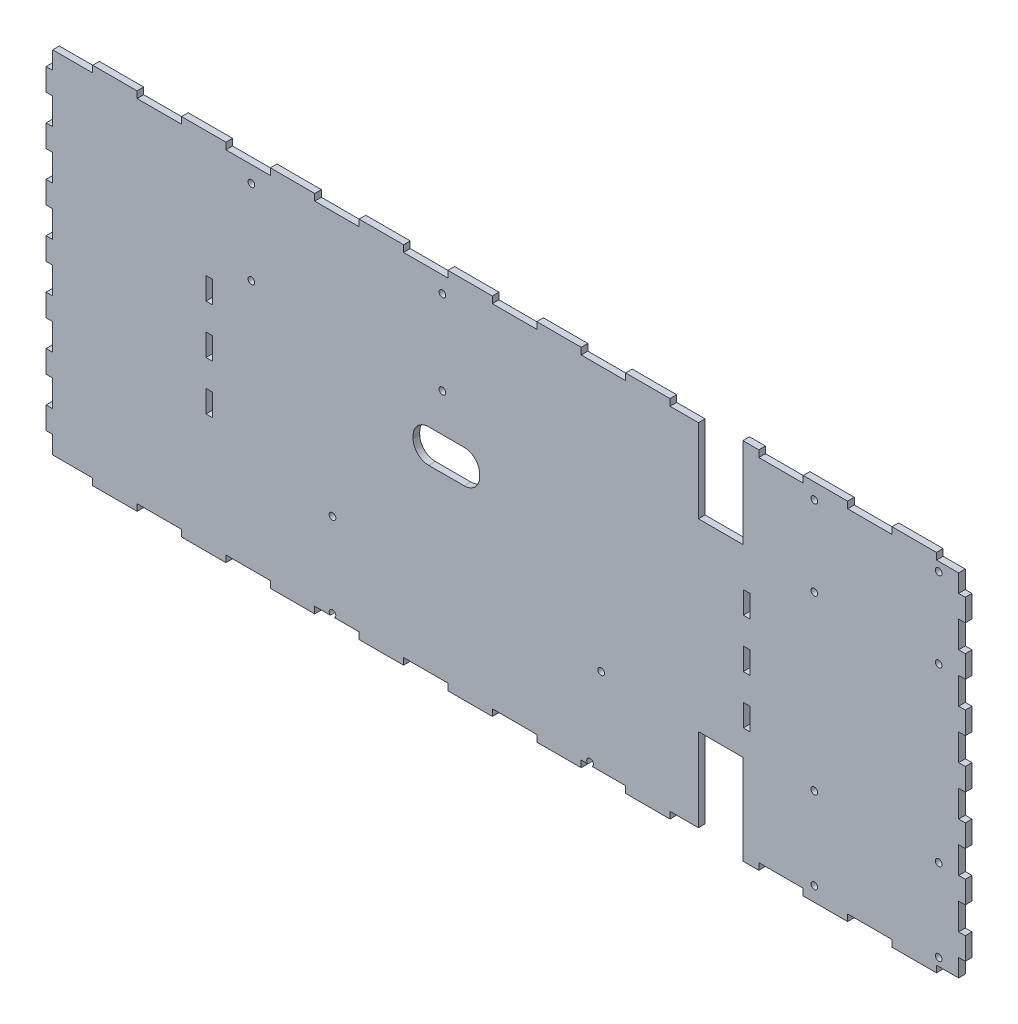
SolidWorks part; units mm, degrees
material "birch 3mm plywood"
ref_plane "Front Plane" through (0, 0, 0) normal (0, 0, 1) x (1, 0, 0)
ref_plane "Top Plane" through (0, 0, 0) normal (0, 1, 0) x (1, 0, 0)
ref_plane "Right Plane" through (0, 0, 0) normal (1, 0, 0) x (0, 0, -1)
sketch "Sketch1" plane through (0, 0, 152) normal (0, 0, 1) x (1, 0, 0)
  line L1 (-207, 82) -> (207, 82)
  line L2 (-207, 82) -> (-207, -82)
  line L3 (-207, -82) -> (207, -82)
  line L4 (207, 82) -> (207, -82)
  line L12 (200, -75) -> (-200, -75) construction
  line L13 (200, 75) -> (200, -75) construction
  line L14 (-200, -75) -> (-200, 75) construction
  line L15 (-200, 75) -> (200, 75) construction
  line L26 (-200, 0) -> (200, 0) construction
  line L31 (-200, 0) -> (200, 0) construction
  point P14 (0, 0)
  point P15 (0, 0)
  point P32 (-47.5, -25.9413)
  point P35 (256.981, -145.9413)
  point P38 (10.8894, 25.9413)
  point P51 (10.8894, -25.9413)
  point P54 (256.981, 145.9413)
  dimension "D1" = 7
  dimension "D2" = 7
  dimension "D3" = 7
  dimension "D4" = 7
  dimension "D5" = 150
  dimension "D6" = 400
extrude "Boss-Extrude1" add sketch "Sketch1" along normal blind 3
sketch "Sketch2" plane through (-207, 0, 0) normal (-1, 0, 0) x (0, 0, 1)
  line L7 (155, -82) -> (152, -82)
  line L8 (152, -82) -> (152, -71)
  line L9 (152, 82) -> (155, 82)
  line L10 (155, 82) -> (155, 71)
  line L11 (152, -61) -> (152, -49)
  line L12 (155, -71) -> (155, -82)
  line L13 (155, -49) -> (155, -61)
  line L14 (152, -39) -> (152, -27)
  line L15 (152, -17) -> (152, -5)
  line L16 (155, -27) -> (155, -39)
  line L17 (155, -5) -> (155, -17)
  line L18 (152, 5) -> (152, 17)
  line L19 (152, 27) -> (152, 39)
  line L20 (155, 17) -> (155, 5)
  line L21 (155, 39) -> (155, 27)
  line L22 (152, 49) -> (152, 61)
  line L23 (152, 71) -> (152, 82)
  line L24 (155, 61) -> (155, 49)
  line L76 (132.5, 88.6) -> (132.5, 93.6)
  line L77 (132.5, 88.6) -> (132.5, 93.6)
  line L78 (129.5, 98.6) -> (128.8771, 98.6)
  line L79 (129.5, 98.6) -> (128.8771, 98.6)
  line L80 (129.5, 82) -> (129.5, 88.6)
  line L81 (129.5, 82) -> (129.5, 88.6)
  line L82 (129.5, 88.6) -> (132.5, 88.6)
  line L83 (129.5, 88.6) -> (132.5, 88.6)
  line L85 (16, 82) -> (16, -82)
  line L102 (129.5, -82) -> (133, -82)
  line L103 (133, -82) -> (133, -79)
  line L104 (133, -79) -> (145, -79)
  line L105 (145, -79) -> (145, -82)
  line L106 (145, -82) -> (155, -82)
  line L107 (155, -82) -> (155, -71)
  line L108 (155, -71) -> (152, -71)
  line L109 (152, -71) -> (152, -61)
  line L110 (152, -61) -> (155, -61)
  line L111 (155, -61) -> (155, -49)
  line L112 (155, -49) -> (152, -49)
  line L113 (152, -49) -> (152, -39)
  line L114 (152, -39) -> (155, -39)
  line L115 (155, -39) -> (155, -27)
  line L116 (155, -27) -> (152, -27)
  line L117 (152, -27) -> (152, -17)
  line L118 (152, -17) -> (155, -17)
  line L119 (155, -17) -> (155, -5)
  line L120 (155, -5) -> (152, -5)
  line L121 (152, -5) -> (152, 5)
  line L122 (152, 5) -> (155, 5)
  line L123 (155, 5) -> (155, 17)
  line L124 (155, 17) -> (152, 17)
  line L125 (152, 17) -> (152, 27)
  line L126 (152, 27) -> (155, 27)
  line L127 (155, 27) -> (155, 39)
  line L128 (155, 39) -> (152, 39)
  line L129 (152, 39) -> (152, 49)
  line L130 (152, 49) -> (155, 49)
  line L131 (155, 49) -> (155, 61)
  line L132 (155, 61) -> (152, 61)
  line L133 (152, 61) -> (152, 71)
  line L134 (152, 71) -> (155, 71)
  line L135 (155, 71) -> (155, 82)
  line L136 (155, 82) -> (145, 82)
  line L137 (145, 82) -> (145, 79)
  line L138 (145, 79) -> (133, 79)
  line L139 (133, 79) -> (133, 82)
  line L140 (133, 82) -> (129.5, 82)
  line L184 (155, -71) -> (152, -71)
  line L186 (152, -61) -> (155, -61)
  line L188 (155, -49) -> (152, -49)
  line L190 (152, -39) -> (155, -39)
  line L192 (155, -27) -> (152, -27)
  line L194 (152, -17) -> (155, -17)
  line L196 (155, -5) -> (152, -5)
  line L198 (152, 5) -> (155, 5)
  line L200 (155, 17) -> (152, 17)
  line L202 (152, 27) -> (155, 27)
  line L204 (155, 39) -> (152, 39)
  line L206 (152, 49) -> (155, 49)
  line L208 (155, 61) -> (152, 61)
  line L210 (152, 71) -> (155, 71)
  line L297 (132.5, 93.6) -> (129.5, 93.6)
  line L298 (132.5, 93.6) -> (129.5, 93.6)
  line L299 (129.5, 93.6) -> (129.5, 98.6)
  line L300 (129.5, 93.6) -> (129.5, 98.6)
  line L301 (128.8771, -98.6) -> (129.5, -98.6)
  line L302 (128.8771, -98.6) -> (129.5, -98.6)
  line L303 (129.5, -98.6) -> (129.5, -93.6)
  line L304 (129.5, -98.6) -> (129.5, -93.6)
  line L305 (129.5, -93.6) -> (132.5, -93.6)
  line L306 (129.5, -93.6) -> (132.5, -93.6)
  line L307 (132.5, -93.6) -> (132.5, -88.6)
  line L308 (132.5, -93.6) -> (132.5, -88.6)
  line L309 (132.5, -88.6) -> (129.5, -88.6)
  line L310 (132.5, -88.6) -> (129.5, -88.6)
  line L311 (129.5, -88.6) -> (129.5, -82)
  line L312 (129.5, -88.6) -> (129.5, -82)
  arc A4 (128.8771, 98.6) -> (16, 82) centre (128.8771, -293.4723) ccw
  arc A5 (128.8771, 98.6) -> (16, 82) centre (128.8771, -293.4723) ccw
  arc A6 (16, -82) -> (128.8771, -98.6) centre (128.8771, 293.4723) ccw
  arc A7 (16, -82) -> (128.8771, -98.6) centre (128.8771, 293.4723) ccw
  line M77 (152, 82) -> (152, -82)
  line M78 (152, -82) -> (155, -82)
  line M79 (155, -82) -> (155, 82)
  line M80 (155, 82) -> (152, 82)
  dimension "D1" = 0
extrude "Cut-Extrude1" cut sketch "Sketch2" against normal blind 3 contours L184 M79 M77 M78 | L188 L186 M79 M77 | L192 L190 M79 M77 | L196 L194 M79 M77 | L200 L198 M79 M77 | L204 L202 M79 M77 | L208 L206 M79 M77 | L210 M77 M79 M80 region at (-207, -76.5, 153.5) region at (-207, -55, 153.5) region at (-207, -33, 153.5) region at (-207, -11, 153.5) region at (-207, 11, 153.5) region at (-207, 33, 153.5) region at (-207, 55, 153.5) region at (-207, 76.5, 153.5)
mirror "Mirror1" about plane through (0, 0, 0) normal (1, 0, 0) of "Cut-Extrude1"
sketch "Sketch3" plane through (0, 82, 0) normal (0, 1, 0) x (1, 0, 0)
  line L92 (174, -152) -> (194, -152)
  line L93 (194, -152) -> (194, -155)
  line L94 (194, -155) -> (204, -155)
  line L97 (207, -45) -> (204, -45)
  line L120 (204, -16) -> (-204, -16)
  line L123 (-204, -45) -> (-207, -45)
  line L146 (-204, -155) -> (-186, -155)
  line L147 (-186, -155) -> (-186, -152)
  line L148 (-186, -152) -> (-166, -152)
  line L149 (-166, -152) -> (-166, -155)
  line L150 (-166, -155) -> (-146, -155)
  line L151 (-146, -155) -> (-146, -152)
  line L152 (-146, -152) -> (-126, -152)
  line L153 (-126, -152) -> (-126, -155)
  line L154 (-126, -155) -> (-106, -155)
  line L155 (-106, -155) -> (-106, -152)
  line L156 (-106, -152) -> (-86, -152)
  line L157 (-86, -152) -> (-86, -155)
  line L158 (-86, -155) -> (-66, -155)
  line L159 (-66, -155) -> (-66, -152)
  line L160 (-66, -152) -> (-46, -152)
  line L161 (-46, -152) -> (-46, -155)
  line L162 (-46, -155) -> (-26, -155)
  line L163 (-26, -155) -> (-26, -152)
  line L164 (-26, -152) -> (-6, -152)
  line L165 (-6, -152) -> (-6, -155)
  line L166 (-6, -155) -> (14, -155)
  line L167 (14, -155) -> (14, -152)
  line L168 (14, -152) -> (34, -152)
  line L169 (34, -152) -> (34, -155)
  line L170 (34, -155) -> (54, -155)
  line L171 (54, -155) -> (54, -152)
  line L172 (54, -152) -> (74, -152)
  line L173 (74, -152) -> (74, -155)
  line L174 (74, -155) -> (94, -155)
  line L175 (94, -155) -> (94, -152)
  line L176 (94, -152) -> (114, -152)
  line L177 (114, -152) -> (114, -155)
  line L178 (114, -155) -> (134, -155)
  line L179 (134, -155) -> (134, -152)
  line L180 (134, -152) -> (154, -152)
  line L181 (154, -152) -> (154, -155)
  line L182 (154, -155) -> (174, -155)
  line L183 (174, -155) -> (174, -152)
  line L184 (174, -152) -> (194, -152)
  line L185 (194, -152) -> (194, -155)
  line L186 (194, -155) -> (204, -155)
  line L212 (204, -16) -> (-204, -16)
  line L238 (-204, -155) -> (-186, -155)
  line L239 (-186, -155) -> (-186, -152)
  line L240 (-186, -152) -> (-166, -152)
  line L241 (-166, -152) -> (-166, -155)
  line L242 (-166, -155) -> (-146, -155)
  line L243 (-146, -155) -> (-146, -152)
  line L244 (-146, -152) -> (-126, -152)
  line L245 (-126, -152) -> (-126, -155)
  line L246 (-126, -155) -> (-106, -155)
  line L247 (-106, -155) -> (-106, -152)
  line L248 (-106, -152) -> (-86, -152)
  line L249 (-86, -152) -> (-86, -155)
  line L250 (-86, -155) -> (-66, -155)
  line L251 (-66, -155) -> (-66, -152)
  line L252 (-66, -152) -> (-46, -152)
  line L253 (-46, -152) -> (-46, -155)
  line L254 (-46, -155) -> (-26, -155)
  line L255 (-26, -155) -> (-26, -152)
  line L256 (-26, -152) -> (-6, -152)
  line L257 (-6, -152) -> (-6, -155)
  line L258 (-6, -155) -> (14, -155)
  line L259 (14, -155) -> (14, -152)
  line L260 (14, -152) -> (34, -152)
  line L261 (34, -152) -> (34, -155)
  line L262 (34, -155) -> (54, -155)
  line L263 (54, -155) -> (54, -152)
  line L264 (54, -152) -> (74, -152)
  line L265 (74, -152) -> (74, -155)
  line L266 (74, -155) -> (94, -155)
  line L267 (94, -155) -> (94, -152)
  line L268 (94, -152) -> (114, -152)
  line L269 (114, -152) -> (114, -155)
  line L270 (114, -155) -> (134, -155)
  line L271 (134, -155) -> (134, -152)
  line L272 (134, -152) -> (154, -152)
  line L273 (154, -152) -> (154, -155)
  line L274 (154, -155) -> (174, -155)
  line L275 (174, -155) -> (174, -152)
  line L576 (-204, -45) -> (-207, -45)
  line L577 (-207, -45) -> (-207, -57)
  line L578 (-207, -45) -> (-207, -57)
  line L579 (-207, -57) -> (-204, -57)
  line L580 (-207, -57) -> (-204, -57)
  line L581 (-204, -57) -> (-204, -67)
  line L582 (-204, -57) -> (-204, -67)
  line L583 (-204, -67) -> (-207, -67)
  line L584 (-204, -67) -> (-207, -67)
  line L585 (-207, -67) -> (-207, -79)
  line L586 (-207, -67) -> (-207, -79)
  line L587 (-207, -79) -> (-204, -79)
  line L588 (-207, -79) -> (-204, -79)
  line L589 (-204, -79) -> (-204, -89)
  line L590 (-204, -79) -> (-204, -89)
  line L591 (-204, -89) -> (-207, -89)
  line L592 (-204, -89) -> (-207, -89)
  line L593 (-207, -89) -> (-207, -101)
  line L594 (-207, -89) -> (-207, -101)
  line L595 (-207, -101) -> (-204, -101)
  line L596 (-207, -101) -> (-204, -101)
  line L597 (-204, -101) -> (-204, -111)
  line L598 (-204, -101) -> (-204, -111)
  line L599 (-204, -111) -> (-207, -111)
  line L600 (-204, -111) -> (-207, -111)
  line L601 (-207, -111) -> (-207, -123)
  line L602 (-207, -111) -> (-207, -123)
  line L603 (-207, -123) -> (-204, -123)
  line L604 (-207, -123) -> (-204, -123)
  line L605 (-204, -123) -> (-204, -133)
  line L606 (-204, -123) -> (-204, -133)
  line L607 (-204, -133) -> (-207, -133)
  line L608 (-204, -133) -> (-207, -133)
  line L609 (-207, -133) -> (-207, -145)
  line L610 (-207, -133) -> (-207, -145)
  line L611 (-207, -145) -> (-204, -145)
  line L612 (-207, -145) -> (-204, -145)
  line L613 (-204, -145) -> (-204, -155)
  line L614 (-204, -145) -> (-204, -155)
  line L615 (-204, -16) -> (-204, -23)
  line L616 (-204, -16) -> (-204, -23)
  line L617 (-204, -23) -> (-207, -23)
  line L618 (-204, -23) -> (-207, -23)
  line L619 (-207, -23) -> (-207, -35)
  line L620 (-207, -23) -> (-207, -35)
  line L621 (-207, -35) -> (-204, -35)
  line L622 (-207, -35) -> (-204, -35)
  line L623 (-204, -35) -> (-204, -45)
  line L624 (-204, -35) -> (-204, -45)
  line L741 (207, -45) -> (204, -45)
  line L742 (204, -45) -> (204, -35)
  line L743 (204, -45) -> (204, -35)
  line L744 (204, -35) -> (207, -35)
  line L745 (204, -35) -> (207, -35)
  line L746 (207, -35) -> (207, -23)
  line L747 (207, -35) -> (207, -23)
  line L748 (207, -23) -> (204, -23)
  line L749 (207, -23) -> (204, -23)
  line L750 (204, -23) -> (204, -16)
  line L751 (204, -23) -> (204, -16)
  line L752 (204, -155) -> (204, -145)
  line L753 (204, -155) -> (204, -145)
  line L754 (204, -145) -> (207, -145)
  line L755 (204, -145) -> (207, -145)
  line L756 (207, -145) -> (207, -133)
  line L757 (207, -145) -> (207, -133)
  line L758 (207, -133) -> (204, -133)
  line L759 (207, -133) -> (204, -133)
  line L760 (204, -133) -> (204, -123)
  line L761 (204, -133) -> (204, -123)
  line L762 (204, -123) -> (207, -123)
  line L763 (204, -123) -> (207, -123)
  line L764 (207, -123) -> (207, -111)
  line L765 (207, -123) -> (207, -111)
  line L766 (207, -111) -> (204, -111)
  line L767 (207, -111) -> (204, -111)
  line L768 (204, -111) -> (204, -101)
  line L769 (204, -111) -> (204, -101)
  line L770 (204, -101) -> (207, -101)
  line L771 (204, -101) -> (207, -101)
  line L772 (207, -101) -> (207, -89)
  line L773 (207, -101) -> (207, -89)
  line L774 (207, -89) -> (204, -89)
  line L775 (207, -89) -> (204, -89)
  line L776 (204, -89) -> (204, -79)
  line L777 (204, -89) -> (204, -79)
  line L778 (204, -79) -> (207, -79)
  line L779 (204, -79) -> (207, -79)
  line L780 (207, -79) -> (207, -67)
  line L781 (207, -79) -> (207, -67)
  line L782 (207, -67) -> (204, -67)
  line L783 (207, -67) -> (204, -67)
  line L784 (204, -67) -> (204, -57)
  line L785 (204, -67) -> (204, -57)
  line L786 (204, -57) -> (207, -57)
  line L787 (204, -57) -> (207, -57)
  line L788 (207, -57) -> (207, -45)
  line L789 (207, -57) -> (207, -45)
  dimension "D1" = 0
extrude "Cut-Extrude2" cut sketch "Sketch3" against normal blind 3
mirror "Mirror2" about plane through (0, 0, 0) normal (0, 1, 0) of "Cut-Extrude2"
sketch "Sketch4" plane through (0, 0, 155) normal (0, 0, 1) x (1, 0, 0)
  line L0 (-132, 25.512) -> (-132, 15.512) construction
  line L1 (-132, 15.512) -> (-135, 15.512) construction
  line L2 (-135, 15.512) -> (-135, 25.512) construction
  line L3 (-135, 25.512) -> (-132, 25.512) construction
  line L4 (-132, 3.512) -> (-132, -6.488) construction
  line L5 (-132, -6.488) -> (-135, -6.488) construction
  line L6 (-135, -6.488) -> (-135, 3.512) construction
  line L7 (-135, 3.512) -> (-132, 3.512) construction
  line L8 (-132, -18.488) -> (-132, -28.488) construction
  line L9 (-132, -28.488) -> (-135, -28.488) construction
  line L10 (-135, -28.488) -> (-135, -18.488) construction
  line L11 (-135, -18.488) -> (-132, -18.488) construction
  line L12 (-132, 25.512) -> (-132, 15.512)
  line L13 (-132, 15.512) -> (-135, 15.512)
  line L14 (-135, 15.512) -> (-135, 25.512)
  line L15 (-135, 25.512) -> (-132, 25.512)
  line L16 (-132, 3.512) -> (-132, -6.488)
  line L17 (-132, -6.488) -> (-135, -6.488)
  line L18 (-135, -6.488) -> (-135, 3.512)
  line L19 (-135, 3.512) -> (-132, 3.512)
  line L20 (-132, -18.488) -> (-132, -28.488)
  line L21 (-132, -28.488) -> (-135, -28.488)
  line L22 (-135, -28.488) -> (-135, -18.488)
  line L23 (-135, -18.488) -> (-132, -18.488)
  line L24 (110, 24.0241) -> (110, 14.0241) construction
  line L25 (110, 14.0241) -> (107, 14.0241) construction
  line L26 (107, 14.0241) -> (107, 24.0241) construction
  line L27 (107, 24.0241) -> (110, 24.0241) construction
  line L28 (110, 2.0241) -> (110, -7.9759) construction
  line L29 (110, -7.9759) -> (107, -7.9759) construction
  line L30 (107, -7.9759) -> (107, 2.0241) construction
  line L31 (107, 2.0241) -> (110, 2.0241) construction
  line L32 (110, -19.9759) -> (110, -29.9759) construction
  line L33 (110, -29.9759) -> (107, -29.9759) construction
  line L34 (107, -29.9759) -> (107, -19.9759) construction
  line L35 (107, -19.9759) -> (110, -19.9759) construction
  line L36 (110, 24.0241) -> (110, 14.0241)
  line L37 (110, 14.0241) -> (107, 14.0241)
  line L38 (107, 14.0241) -> (107, 24.0241)
  line L39 (107, 24.0241) -> (110, 24.0241)
  line L40 (110, 2.0241) -> (110, -7.9759)
  line L41 (110, -7.9759) -> (107, -7.9759)
  line L42 (107, -7.9759) -> (107, 2.0241)
  line L43 (107, 2.0241) -> (110, 2.0241)
  line L44 (110, -19.9759) -> (110, -29.9759)
  line L45 (110, -29.9759) -> (107, -29.9759)
  line L46 (107, -29.9759) -> (107, -19.9759)
  line L47 (107, -19.9759) -> (110, -19.9759)
  circle A0 centre (139, 39) radius 1.5 construction
  circle A1 centre (195, 39) radius 1.5 construction
  circle A2 centre (195, 75) radius 1.5 construction
  circle A3 centre (139, 75) radius 1.5 construction
  circle A4 centre (-114.5, 33.7241) radius 1.5 construction
  circle A5 centre (-114.5, 71.6241) radius 1.5 construction
  circle A6 centre (-28.5, 33.7241) radius 1.5 construction
  circle A7 centre (-28.5, 71.6241) radius 1.5 construction
  circle A8 centre (139, 39) radius 1.5
  circle A9 centre (195, 39) radius 1.5
  circle A10 centre (195, 75) radius 1.5
  circle A11 centre (139, 75) radius 1.5
  circle A16 centre (139, -75.5) radius 1.5
  circle A17 centre (195, -75.5) radius 1.5
  circle A18 centre (195, -38.5) radius 1.5
  circle A19 centre (139, -38.5) radius 1.5
  circle A20 centre (-114.5, 33.7241) radius 1.5
  circle A21 centre (-114.5, 71.6241) radius 1.5
  circle A22 centre (-28.5, 33.7241) radius 1.5
  circle A23 centre (-28.5, 71.6241) radius 1.5
  circle A24 centre (38, -77.8759) radius 1.5 construction
  circle A25 centre (43, -39.9759) radius 1.5 construction
  circle A26 centre (-78, -77.8759) radius 1.5 construction
  circle A27 centre (-78, -39.9759) radius 1.5 construction
  circle A28 centre (38, -77.8759) radius 1.5
  circle A29 centre (43, -39.9759) radius 1.5
  circle A30 centre (-78, -77.8759) radius 1.5
  circle A31 centre (-78, -39.9759) radius 1.5
extrude "Cut-Extrude3" cut sketch "Sketch4" against normal blind 10
sketch "Sketch5" plane through (0, 0, 155) normal (0, 0, 1) x (1, 0, 0)
  line L0 (86.8, 82) -> (86.8, 79) construction
  line L1 (-34.7, 1.6241) -> (-18.7, 1.6241)
  line L2 (-41.7, 8.6241) -> (-41.7, 9.6241)
  line L3 (-34.7, 16.6241) -> (-18.7, 16.6241)
  line L4 (-11.7, 9.6241) -> (-11.7, 8.6241)
  line L5 (-27.7, 1.6241) -> (0, 1.6241) construction
  line L6 (86.8, 41.5) -> (106.8, 41.5)
  line L7 (-27.7, 1.6241) -> (-27.7, -10.7759) construction
  line L8 (86.8, 41.5) -> (86.8, 82)
  line L9 (86.8, 82) -> (106.8, 82)
  line L10 (106.8, 41.5) -> (106.8, 82)
  line L12 (114, 82) -> (94, 82) construction
  line L13 (64, 82) -> (64, -82) construction
  line L14 (74, 82) -> (54, 82) construction
  line L15 (54, -82) -> (74, -82) construction
  line L16 (64, -82) -> (64, 0) construction
  line L17 (64, 0) -> (99.6083, 0) construction
  line L18 (106.8, -41.5) -> (106.8, -82)
  line L19 (86.8, -82) -> (106.8, -82)
  line L20 (86.8, -41.5) -> (106.8, -41.5)
  line L21 (86.8, -41.5) -> (86.8, -82)
  arc A0 (-34.7, 16.6241) -> (-41.7, 9.6241) centre (-34.7, 9.6241) ccw
  arc A1 (-11.7, 9.6241) -> (-18.7, 16.6241) centre (-18.7, 9.6241) ccw
  arc A2 (-18.7, 1.6241) -> (-11.7, 8.6241) centre (-18.7, 8.6241) ccw
  arc A3 (-34.7, 1.6241) -> (-41.7, 8.6241) centre (-34.7, 8.6241) cw
  point P16 (-11.7, 1.6241)
  point P19 (-41.7, 1.6241)
  dimension "D4" = 7
  dimension "D1" = 30
  dimension "D2" = 15
  dimension "D3" = 16
  dimension "D5" = 20
  dimension "D6" = 40.5
extrude "Cut-Extrude4" cut sketch "Sketch5" against normal blind 10
sketch "Sketch6" plane through (0, 0, 155) normal (0, 0, 1) x (1, 0, 0)
  line L0 (-204, 79) -> (-186, 79) construction
  line L1 (-170.906, 59) -> (-176.6795, 69)
  line L2 (-176.6795, 69) -> (-188.2265, 69)
  line L3 (-188.2265, 69) -> (-194, 59)
  line L4 (-194, 59) -> (-188.2265, 49)
  line L5 (-188.2265, 49) -> (-176.6795, 49)
  line L6 (-176.6795, 49) -> (-170.906, 59)
  line L7 (-204, 49) -> (-204, 61) construction
  line L8 (-144.9252, 44) -> (-150.6987, 54)
  line L9 (-150.6987, 54) -> (-162.2457, 54)
  line L10 (-162.2457, 54) -> (-168.0192, 44)
  line L11 (-168.0192, 44) -> (-162.2457, 34)
  line L12 (-162.2457, 34) -> (-150.6987, 34)
  line L13 (-150.6987, 34) -> (-144.9252, 44)
  line L14 (-120.906, 59) -> (-126.6795, 69)
  line L15 (-126.6795, 69) -> (-138.2265, 69)
  line L16 (-138.2265, 69) -> (-144, 59)
  line L17 (-144, 59) -> (-138.2265, 49)
  line L18 (-138.2265, 49) -> (-126.6795, 49)
  line L19 (-126.6795, 49) -> (-120.906, 59)
  line L20 (-94.9252, 44) -> (-100.6987, 54)
  line L21 (-100.6987, 54) -> (-112.2457, 54)
  line L22 (-112.2457, 54) -> (-118.0192, 44)
  line L23 (-118.0192, 44) -> (-112.2457, 34)
  line L24 (-112.2457, 34) -> (-100.6987, 34)
  line L25 (-100.6987, 34) -> (-94.9252, 44)
  line L26 (-70.906, 59) -> (-76.6795, 69)
  line L27 (-76.6795, 69) -> (-88.2265, 69)
  line L28 (-88.2265, 69) -> (-94, 59)
  line L29 (-94, 59) -> (-88.2265, 49)
  line L30 (-88.2265, 49) -> (-76.6795, 49)
  line L31 (-76.6795, 49) -> (-70.906, 59)
  line L32 (-44.9252, 44) -> (-50.6987, 54)
  line L33 (-50.6987, 54) -> (-62.2457, 54)
  line L34 (-62.2457, 54) -> (-68.0192, 44)
  line L35 (-68.0192, 44) -> (-62.2457, 34)
  line L36 (-62.2457, 34) -> (-50.6987, 34)
  line L37 (-50.6987, 34) -> (-44.9252, 44)
  line L38 (-20.906, 59) -> (-26.6795, 69)
  line L39 (-26.6795, 69) -> (-38.2265, 69)
  line L40 (-38.2265, 69) -> (-44, 59)
  line L41 (-44, 59) -> (-38.2265, 49)
  line L42 (-38.2265, 49) -> (-26.6795, 49)
  line L43 (-26.6795, 49) -> (-20.906, 59)
  line L44 (5.0748, 44) -> (-0.6987, 54)
  line L45 (-0.6987, 54) -> (-12.2457, 54)
  line L46 (-12.2457, 54) -> (-18.0192, 44)
  line L47 (-18.0192, 44) -> (-12.2457, 34)
  line L48 (-12.2457, 34) -> (-0.6987, 34)
  line L49 (-0.6987, 34) -> (5.0748, 44)
  line L50 (29.094, 59) -> (23.3205, 69)
  line L51 (23.3205, 69) -> (11.7735, 69)
  line L52 (11.7735, 69) -> (6, 59)
  line L53 (6, 59) -> (11.7735, 49)
  line L54 (11.7735, 49) -> (23.3205, 49)
  line L55 (23.3205, 49) -> (29.094, 59)
  line L56 (55.0748, 44) -> (49.3013, 54)
  line L57 (49.3013, 54) -> (37.7543, 54)
  line L58 (37.7543, 54) -> (31.9808, 44)
  line L59 (31.9808, 44) -> (37.7543, 34)
  line L60 (37.7543, 34) -> (49.3013, 34)
  line L61 (49.3013, 34) -> (55.0748, 44)
  line L62 (79.094, 59) -> (73.3205, 69)
  line L63 (73.3205, 69) -> (61.7735, 69)
  line L64 (61.7735, 69) -> (56, 59)
  line L65 (56, 59) -> (61.7735, 49)
  line L66 (61.7735, 49) -> (73.3205, 49)
  line L67 (73.3205, 49) -> (79.094, 59)
  line L68 (105.0748, 44) -> (99.3013, 54)
  line L69 (99.3013, 54) -> (87.7543, 54)
  line L70 (87.7543, 54) -> (81.9808, 44)
  line L71 (81.9808, 44) -> (87.7543, 34)
  line L72 (87.7543, 34) -> (99.3013, 34)
  line L73 (99.3013, 34) -> (105.0748, 44)
  line L74 (129.094, 59) -> (123.3205, 69)
  line L75 (123.3205, 69) -> (111.7735, 69)
  line L76 (111.7735, 69) -> (106, 59)
  line L77 (106, 59) -> (111.7735, 49)
  line L78 (111.7735, 49) -> (123.3205, 49)
  line L79 (123.3205, 49) -> (129.094, 59)
  line L80 (155.0748, 44) -> (149.3013, 54)
  line L81 (149.3013, 54) -> (137.7543, 54)
  line L82 (137.7543, 54) -> (134.8675, 49)
  line L85 (152.188, 39) -> (155.0748, 44)
  line L86 (179.094, 59) -> (173.3205, 69)
  line L87 (173.3205, 69) -> (161.7735, 69)
  line L88 (161.7735, 69) -> (156, 59)
  line L89 (156, 59) -> (161.7735, 49)
  line L90 (161.7735, 49) -> (173.3205, 49)
  line L91 (173.3205, 49) -> (179.094, 59)
  line L93 (193.5278, 54) -> (187.7543, 54)
  line L94 (187.7543, 54) -> (181.9808, 44)
  line L95 (181.9808, 44) -> (184.8675, 39)
  line L98 (-123.7927, 34) -> (-126.6795, 39)
  line L99 (-126.6795, 39) -> (-138.2265, 39)
  line L100 (-138.2265, 39) -> (-141.1132, 34)
  line L104 (-94.9252, 14) -> (-100.6987, 24)
  line L105 (-100.6987, 24) -> (-112.2457, 24)
  line L106 (-112.2457, 24) -> (-118.0192, 14)
  line L107 (-118.0192, 14) -> (-112.2457, 4)
  line L108 (-112.2457, 4) -> (-100.6987, 4)
  line L109 (-100.6987, 4) -> (-94.9252, 14)
  line L112 (-88.2265, 39) -> (-94, 29)
  line L113 (-94, 29) -> (-88.2265, 19)
  line L114 (-88.2265, 19) -> (-76.6795, 19)
  line L116 (-44.9252, 14) -> (-50.6987, 24)
  line L117 (-50.6987, 24) -> (-62.2457, 24)
  line L118 (-62.2457, 24) -> (-68.0192, 14)
  line L119 (-68.0192, 14) -> (-62.2457, 4)
  line L120 (-62.2457, 4) -> (-50.6987, 4)
  line L121 (-50.6987, 4) -> (-44.9252, 14)
  line L123 (-32.453, 39) -> (-38.2265, 39)
  line L124 (-38.2265, 39) -> (-44, 29)
  line L125 (-44, 29) -> (-41.1132, 24)
  line L128 (5.0748, 14) -> (-0.6987, 24)
  line L129 (-0.6987, 24) -> (-6.4722, 24)
  line L132 (-6.4722, 4) -> (-0.6987, 4)
  line L133 (-0.6987, 4) -> (5.0748, 14)
  line L134 (29.094, 29) -> (23.3205, 39)
  line L135 (23.3205, 39) -> (11.7735, 39)
  line L136 (11.7735, 39) -> (6, 29)
  line L137 (6, 29) -> (11.7735, 19)
  line L138 (11.7735, 19) -> (23.3205, 19)
  line L139 (23.3205, 19) -> (29.094, 29)
  line L140 (55.0748, 14) -> (49.3013, 24)
  line L141 (49.3013, 24) -> (37.7543, 24)
  line L142 (37.7543, 24) -> (31.9808, 14)
  line L143 (31.9808, 14) -> (37.7543, 4)
  line L144 (37.7543, 4) -> (49.3013, 4)
  line L145 (49.3013, 4) -> (55.0748, 14)
  line L146 (79.094, 29) -> (73.3205, 39)
  line L147 (73.3205, 39) -> (61.7735, 39)
  line L148 (61.7735, 39) -> (56, 29)
  line L149 (56, 29) -> (61.7735, 19)
  line L150 (61.7735, 19) -> (73.3205, 19)
  line L151 (73.3205, 19) -> (79.094, 29)
  line L153 (99.3013, 24) -> (87.7543, 24)
  line L154 (87.7543, 24) -> (81.9808, 14)
  line L155 (81.9808, 14) -> (87.7543, 4)
  line L156 (87.7543, 4) -> (99.3013, 4)
  line L158 (129.094, 29) -> (123.3205, 39)
  line L159 (123.3205, 39) -> (117.547, 39)
  line L162 (117.547, 19) -> (123.3205, 19)
  line L163 (123.3205, 19) -> (129.094, 29)
  line L164 (155.0748, 14) -> (149.3013, 24)
  line L165 (149.3013, 24) -> (137.7543, 24)
  line L166 (137.7543, 24) -> (131.9808, 14)
  line L167 (131.9808, 14) -> (137.7543, 4)
  line L168 (137.7543, 4) -> (149.3013, 4)
  line L169 (149.3013, 4) -> (155.0748, 14)
  line L170 (179.094, 29) -> (173.3205, 39)
  line L171 (173.3205, 39) -> (161.7735, 39)
  line L172 (161.7735, 39) -> (156, 29)
  line L173 (156, 29) -> (161.7735, 19)
  line L174 (161.7735, 19) -> (173.3205, 19)
  line L175 (173.3205, 19) -> (179.094, 29)
  line L177 (193.5278, 24) -> (187.7543, 24)
  line L178 (187.7543, 24) -> (181.9808, 14)
  line L179 (181.9808, 14) -> (187.7543, 4)
  line L180 (187.7543, 4) -> (193.5278, 4)
  line L188 (-94.9252, -16) -> (-100.6987, -6)
  line L189 (-100.6987, -6) -> (-112.2457, -6)
  line L190 (-112.2457, -6) -> (-118.0192, -16)
  line L191 (-118.0192, -16) -> (-112.2457, -26)
  line L192 (-112.2457, -26) -> (-100.6987, -26)
  line L193 (-100.6987, -26) -> (-94.9252, -16)
  line L194 (-70.906, -1) -> (-76.6795, 9)
  line L195 (-76.6795, 9) -> (-88.2265, 9)
  line L196 (-88.2265, 9) -> (-94, -1)
  line L197 (-94, -1) -> (-88.2265, -11)
  line L198 (-88.2265, -11) -> (-76.6795, -11)
  line L199 (-76.6795, -11) -> (-70.906, -1)
  line L200 (-44.9252, -16) -> (-50.6987, -6)
  line L201 (-50.6987, -6) -> (-62.2457, -6)
  line L202 (-62.2457, -6) -> (-68.0192, -16)
  line L203 (-68.0192, -16) -> (-62.2457, -26)
  line L204 (-62.2457, -26) -> (-50.6987, -26)
  line L205 (-50.6987, -26) -> (-44.9252, -16)
  line L209 (-44, -1) -> (-38.2265, -11)
  line L210 (-38.2265, -11) -> (-26.6795, -11)
  line L211 (-26.6795, -11) -> (-20.906, -1)
  line L212 (5.0748, -16) -> (-0.6987, -6)
  line L213 (-0.6987, -6) -> (-12.2457, -6)
  line L214 (-12.2457, -6) -> (-18.0192, -16)
  line L215 (-18.0192, -16) -> (-12.2457, -26)
  line L216 (-12.2457, -26) -> (-0.6987, -26)
  line L217 (-0.6987, -26) -> (5.0748, -16)
  line L218 (29.094, -1) -> (23.3205, 9)
  line L219 (23.3205, 9) -> (11.7735, 9)
  line L220 (11.7735, 9) -> (6, -1)
  line L221 (6, -1) -> (11.7735, -11)
  line L222 (11.7735, -11) -> (23.3205, -11)
  line L223 (23.3205, -11) -> (29.094, -1)
  line L224 (55.0748, -16) -> (49.3013, -6)
  line L225 (49.3013, -6) -> (37.7543, -6)
  line L226 (37.7543, -6) -> (31.9808, -16)
  line L227 (31.9808, -16) -> (37.7543, -26)
  line L228 (37.7543, -26) -> (49.3013, -26)
  line L229 (49.3013, -26) -> (55.0748, -16)
  line L230 (79.094, -1) -> (73.3205, 9)
  line L231 (73.3205, 9) -> (61.7735, 9)
  line L232 (61.7735, 9) -> (56, -1)
  line L233 (56, -1) -> (61.7735, -11)
  line L234 (61.7735, -11) -> (73.3205, -11)
  line L235 (73.3205, -11) -> (79.094, -1)
  line L237 (99.3013, -6) -> (87.7543, -6)
  line L238 (87.7543, -6) -> (81.9808, -16)
  line L239 (81.9808, -16) -> (87.7543, -26)
  line L240 (87.7543, -26) -> (99.3013, -26)
  line L242 (129.094, -1) -> (123.3205, 9)
  line L243 (123.3205, 9) -> (117.547, 9)
  line L246 (117.547, -11) -> (123.3205, -11)
  line L247 (123.3205, -11) -> (129.094, -1)
  line L248 (155.0748, -16) -> (149.3013, -6)
  line L249 (149.3013, -6) -> (137.7543, -6)
  line L250 (137.7543, -6) -> (131.9808, -16)
  line L251 (131.9808, -16) -> (137.7543, -26)
  line L252 (137.7543, -26) -> (149.3013, -26)
  line L253 (149.3013, -26) -> (155.0748, -16)
  line L254 (179.094, -1) -> (173.3205, 9)
  line L255 (173.3205, 9) -> (161.7735, 9)
  line L256 (161.7735, 9) -> (156, -1)
  line L257 (156, -1) -> (161.7735, -11)
  line L258 (161.7735, -11) -> (173.3205, -11)
  line L259 (173.3205, -11) -> (179.094, -1)
  line L261 (193.5278, -6) -> (187.7543, -6)
  line L262 (187.7543, -6) -> (181.9808, -16)
  line L263 (181.9808, -16) -> (187.7543, -26)
  line L264 (187.7543, -26) -> (193.5278, -26)
  line L269 (-144, -31) -> (-138.2265, -41)
  line L270 (-138.2265, -41) -> (-126.6795, -41)
  line L271 (-126.6795, -41) -> (-120.906, -31)
  line L272 (-94.9252, -46) -> (-100.6987, -36)
  line L273 (-100.6987, -36) -> (-112.2457, -36)
  line L274 (-112.2457, -36) -> (-118.0192, -46)
  line L275 (-118.0192, -46) -> (-112.2457, -56)
  line L276 (-112.2457, -56) -> (-100.6987, -56)
  line L277 (-100.6987, -56) -> (-94.9252, -46)
  line L278 (-73.7927, -26) -> (-76.6795, -21)
  line L279 (-76.6795, -21) -> (-88.2265, -21)
  line L280 (-88.2265, -21) -> (-94, -31)
  line L281 (-94, -31) -> (-91.1132, -36)
  line L284 (-44.9252, -46) -> (-50.6987, -36)
  line L285 (-50.6987, -36) -> (-62.2457, -36)
  line L286 (-62.2457, -36) -> (-68.0192, -46)
  line L287 (-68.0192, -46) -> (-62.2457, -56)
  line L288 (-62.2457, -56) -> (-50.6987, -56)
  line L289 (-50.6987, -56) -> (-44.9252, -46)
  line L290 (-23.7927, -26) -> (-26.6795, -21)
  line L291 (-26.6795, -21) -> (-38.2265, -21)
  line L292 (-38.2265, -21) -> (-44, -31)
  line L293 (-44, -31) -> (-38.2265, -41)
  line L294 (-38.2265, -41) -> (-32.453, -41)
  line L296 (5.0748, -46) -> (-0.6987, -36)
  line L297 (-0.6987, -36) -> (-12.2457, -36)
  line L298 (-12.2457, -36) -> (-18.0192, -46)
  line L299 (-18.0192, -46) -> (-12.2457, -56)
  line L300 (-12.2457, -56) -> (-0.6987, -56)
  line L301 (-0.6987, -56) -> (5.0748, -46)
  line L302 (29.094, -31) -> (23.3205, -21)
  line L303 (23.3205, -21) -> (11.7735, -21)
  line L304 (11.7735, -21) -> (6, -31)
  line L305 (6, -31) -> (11.7735, -41)
  line L306 (11.7735, -41) -> (23.3205, -41)
  line L307 (23.3205, -41) -> (29.094, -31)
  line L308 (55.0748, -46) -> (49.3013, -36)
  line L309 (49.3013, -36) -> (37.7543, -36)
  line L310 (37.7543, -36) -> (31.9808, -46)
  line L311 (31.9808, -46) -> (37.7543, -56)
  line L312 (37.7543, -56) -> (49.3013, -56)
  line L313 (49.3013, -56) -> (55.0748, -46)
  line L314 (79.094, -31) -> (73.3205, -21)
  line L315 (73.3205, -21) -> (61.7735, -21)
  line L316 (61.7735, -21) -> (56, -31)
  line L317 (56, -31) -> (61.7735, -41)
  line L318 (61.7735, -41) -> (73.3205, -41)
  line L319 (73.3205, -41) -> (79.094, -31)
  line L320 (105.0748, -46) -> (99.3013, -36)
  line L321 (99.3013, -36) -> (87.7543, -36)
  line L322 (87.7543, -36) -> (81.9808, -46)
  line L323 (81.9808, -46) -> (87.7543, -56)
  line L324 (87.7543, -56) -> (99.3013, -56)
  line L325 (99.3013, -56) -> (105.0748, -46)
  line L326 (129.094, -31) -> (123.3205, -21)
  line L329 (108.8868, -36) -> (111.7735, -41)
  line L330 (111.7735, -41) -> (123.3205, -41)
  line L331 (123.3205, -41) -> (129.094, -31)
  line L332 (155.0748, -46) -> (152.188, -41)
  line L335 (134.8675, -51) -> (137.7543, -56)
  line L336 (137.7543, -56) -> (149.3013, -56)
  line L337 (149.3013, -56) -> (155.0748, -46)
  line L338 (179.094, -31) -> (173.3205, -21)
  line L339 (173.3205, -21) -> (161.7735, -21)
  line L340 (161.7735, -21) -> (156, -31)
  line L341 (156, -31) -> (161.7735, -41)
  line L342 (161.7735, -41) -> (173.3205, -41)
  line L343 (173.3205, -41) -> (179.094, -31)
  line L346 (184.8675, -41) -> (181.9808, -46)
  line L347 (181.9808, -46) -> (187.7543, -56)
  line L348 (187.7543, -56) -> (193.5278, -56)
  line L350 (-120.906, -61) -> (-126.6795, -51)
  line L351 (-126.6795, -51) -> (-138.2265, -51)
  line L352 (-138.2265, -51) -> (-144, -61)
  line L353 (-144, -61) -> (-138.2265, -71)
  line L354 (-138.2265, -71) -> (-126.6795, -71)
  line L355 (-126.6795, -71) -> (-120.906, -61)
  line L362 (-70.906, -61) -> (-76.6795, -51)
  line L363 (-76.6795, -51) -> (-88.2265, -51)
  line L364 (-88.2265, -51) -> (-94, -61)
  line L365 (-94, -61) -> (-88.2265, -71)
  line L366 (-88.2265, -71) -> (-76.6795, -71)
  line L367 (-76.6795, -71) -> (-70.906, -61)
  line L374 (-20.906, -61) -> (-26.6795, -51)
  line L375 (-26.6795, -51) -> (-38.2265, -51)
  line L376 (-38.2265, -51) -> (-44, -61)
  line L377 (-44, -61) -> (-38.2265, -71)
  line L378 (-38.2265, -71) -> (-26.6795, -71)
  line L379 (-26.6795, -71) -> (-20.906, -61)
  line L386 (29.094, -61) -> (23.3205, -51)
  line L387 (23.3205, -51) -> (11.7735, -51)
  line L388 (11.7735, -51) -> (6, -61)
  line L389 (6, -61) -> (11.7735, -71)
  line L390 (11.7735, -71) -> (23.3205, -71)
  line L391 (23.3205, -71) -> (29.094, -61)
  line L398 (79.094, -61) -> (73.3205, -51)
  line L399 (73.3205, -51) -> (61.7735, -51)
  line L400 (61.7735, -51) -> (56, -61)
  line L401 (56, -61) -> (61.7735, -71)
  line L402 (61.7735, -71) -> (73.3205, -71)
  line L403 (73.3205, -71) -> (79.094, -61)
  line L410 (129.094, -61) -> (123.3205, -51)
  line L411 (123.3205, -51) -> (111.7735, -51)
  line L412 (111.7735, -51) -> (106, -61)
  line L413 (106, -61) -> (111.7735, -71)
  line L414 (111.7735, -71) -> (123.3205, -71)
  line L415 (123.3205, -71) -> (129.094, -61)
  line L422 (179.094, -61) -> (173.3205, -51)
  line L423 (173.3205, -51) -> (161.7735, -51)
  line L424 (161.7735, -51) -> (156, -61)
  line L425 (156, -61) -> (161.7735, -71)
  line L426 (161.7735, -71) -> (173.3205, -71)
  line L427 (173.3205, -71) -> (179.094, -61)
  line L434 (-170.906, 29) -> (-176.6795, 39)
  line L435 (-176.6795, 39) -> (-188.2265, 39)
  line L436 (-188.2265, 39) -> (-194, 29)
  line L437 (-194, 29) -> (-188.2265, 19)
  line L438 (-188.2265, 19) -> (-176.6795, 19)
  line L439 (-176.6795, 19) -> (-170.906, 29)
  line L440 (-144.9252, 14) -> (-150.6987, 24)
  line L441 (-150.6987, 24) -> (-162.2457, 24)
  line L442 (-162.2457, 24) -> (-168.0192, 14)
  line L443 (-168.0192, 14) -> (-162.2457, 4)
  line L444 (-162.2457, 4) -> (-150.6987, 4)
  line L445 (-150.6987, 4) -> (-144.9252, 14)
  line L446 (-170.906, -1) -> (-176.6795, 9)
  line L447 (-176.6795, 9) -> (-188.2265, 9)
  line L448 (-188.2265, 9) -> (-194, -1)
  line L449 (-194, -1) -> (-188.2265, -11)
  line L450 (-188.2265, -11) -> (-176.6795, -11)
  line L451 (-176.6795, -11) -> (-170.906, -1)
  line L452 (-144.9252, -16) -> (-150.6987, -6)
  line L453 (-150.6987, -6) -> (-162.2457, -6)
  line L454 (-162.2457, -6) -> (-168.0192, -16)
  line L455 (-168.0192, -16) -> (-162.2457, -26)
  line L456 (-162.2457, -26) -> (-150.6987, -26)
  line L457 (-150.6987, -26) -> (-144.9252, -16)
  line L458 (-170.906, -31) -> (-176.6795, -21)
  line L459 (-176.6795, -21) -> (-188.2265, -21)
  line L460 (-188.2265, -21) -> (-194, -31)
  line L461 (-194, -31) -> (-188.2265, -41)
  line L462 (-188.2265, -41) -> (-176.6795, -41)
  line L463 (-176.6795, -41) -> (-170.906, -31)
  line L464 (-144.9252, -46) -> (-150.6987, -36)
  line L465 (-150.6987, -36) -> (-162.2457, -36)
  line L466 (-162.2457, -36) -> (-168.0192, -46)
  line L467 (-168.0192, -46) -> (-162.2457, -56)
  line L468 (-162.2457, -56) -> (-150.6987, -56)
  line L469 (-150.6987, -56) -> (-144.9252, -46)
  line L470 (-170.906, -61) -> (-176.6795, -51)
  line L471 (-176.6795, -51) -> (-188.2265, -51)
  line L472 (-188.2265, -51) -> (-194, -61)
  line L473 (-194, -61) -> (-188.2265, -71)
  line L474 (-188.2265, -71) -> (-176.6795, -71)
  line L475 (-176.6795, -71) -> (-170.906, -61)
  line L482 (-144.9252, -76) -> (-150.6987, -66) [skipped]
  line L483 (-150.6987, -66) -> (-162.2457, -66) [skipped]
  line L484 (-162.2457, -66) -> (-168.0192, -76) [skipped]
  line L485 (-168.0192, -76) -> (-162.2457, -86) [skipped]
  line L486 (-162.2457, -86) -> (-150.6987, -86) [skipped]
  line L487 (-150.6987, -86) -> (-144.9252, -76) [skipped]
  line L488 (-94.9252, -76) -> (-100.6987, -66) [skipped]
  line L489 (-100.6987, -66) -> (-112.2457, -66) [skipped]
  line L490 (-112.2457, -66) -> (-118.0192, -76) [skipped]
  line L491 (-118.0192, -76) -> (-112.2457, -86) [skipped]
  line L492 (-112.2457, -86) -> (-100.6987, -86) [skipped]
  line L493 (-100.6987, -86) -> (-94.9252, -76) [skipped]
  line L494 (-44.9252, -76) -> (-50.6987, -66) [skipped]
  line L495 (-50.6987, -66) -> (-62.2457, -66) [skipped]
  line L496 (-62.2457, -66) -> (-68.0192, -76) [skipped]
  line L497 (-68.0192, -76) -> (-62.2457, -86) [skipped]
  line L498 (-62.2457, -86) -> (-50.6987, -86) [skipped]
  line L499 (-50.6987, -86) -> (-44.9252, -76) [skipped]
  line L500 (5.0748, -76) -> (-0.6987, -66) [skipped]
  line L501 (-0.6987, -66) -> (-12.2457, -66) [skipped]
  line L502 (-12.2457, -66) -> (-18.0192, -76) [skipped]
  line L503 (-18.0192, -76) -> (-12.2457, -86) [skipped]
  line L504 (-12.2457, -86) -> (-0.6987, -86) [skipped]
  line L505 (-0.6987, -86) -> (5.0748, -76) [skipped]
  line L506 (55.0748, -76) -> (49.3013, -66) [skipped]
  line L507 (49.3013, -66) -> (37.7543, -66) [skipped]
  line L508 (37.7543, -66) -> (31.9808, -76) [skipped]
  line L509 (31.9808, -76) -> (37.7543, -86) [skipped]
  line L510 (37.7543, -86) -> (49.3013, -86) [skipped]
  line L511 (49.3013, -86) -> (55.0748, -76) [skipped]
  line L512 (105.0748, -76) -> (99.3013, -66) [skipped]
  line L513 (99.3013, -66) -> (87.7543, -66) [skipped]
  line L514 (87.7543, -66) -> (81.9808, -76) [skipped]
  line L515 (81.9808, -76) -> (87.7543, -86) [skipped]
  line L516 (87.7543, -86) -> (99.3013, -86) [skipped]
  line L517 (99.3013, -86) -> (105.0748, -76) [skipped]
  line L518 (155.0748, -76) -> (149.3013, -66) [skipped]
  line L519 (149.3013, -66) -> (137.7543, -66) [skipped]
  line L520 (137.7543, -66) -> (131.9808, -76) [skipped]
  line L521 (131.9808, -76) -> (137.7543, -86) [skipped]
  line L522 (137.7543, -86) -> (149.3013, -86) [skipped]
  line L523 (149.3013, -86) -> (155.0748, -76) [skipped]
  line L524 (205.0748, -76) -> (199.3013, -66) [skipped]
  line L525 (199.3013, -66) -> (187.7543, -66) [skipped]
  line L526 (187.7543, -66) -> (181.9808, -76) [skipped]
  line L527 (181.9808, -76) -> (187.7543, -86) [skipped]
  line L528 (187.7543, -86) -> (199.3013, -86) [skipped]
  line L529 (199.3013, -86) -> (205.0748, -76) [skipped]
  line L530 (-120.906, -1) -> (-126.6795, 9) [skipped]
  line L531 (-138.2265, 9) -> (-144, -1) [skipped]
  line L532 (-144, -1) -> (-138.2265, -11) [skipped]
  line L533 (-126.6795, -11) -> (-120.906, -1) [skipped]
  line L534 (-126.6795, 9) -> (-138.2265, 9) [skipped]
  line L535 (-138.2265, -11) -> (-126.6795, -11) [skipped]
  line L539 (-165.1325, 69) -> (-162.2457, 64)
  line L540 (-162.2457, 64) -> (-150.6987, 64)
  line L541 (-150.6987, 64) -> (-147.812, 69)
  line L542 (-165.1325, 69) -> (-147.812, 69)
  line L543 (-100.6987, 64) -> (-97.812, 69)
  line L544 (-144.9252, 74) -> (-150.6987, 84) [skipped]
  line L545 (-150.6987, 84) -> (-162.2457, 84) [skipped]
  line L546 (-162.2457, 84) -> (-168.0192, 74) [skipped]
  line L547 (-115.1325, 69) -> (-97.812, 69)
  line L548 (-112.2457, 64) -> (-100.6987, 64)
  line L549 (-115.1325, 69) -> (-112.2457, 64)
  line L550 (-50.6987, 64) -> (-47.812, 69)
  line L551 (-65.1325, 69) -> (-47.812, 69)
  line L552 (-62.2457, 64) -> (-50.6987, 64)
  line L553 (-65.1325, 69) -> (-62.2457, 64)
  line L554 (-0.6987, 64) -> (2.188, 69)
  line L555 (-15.1325, 69) -> (2.188, 69)
  line L556 (-12.2457, 64) -> (-0.6987, 64)
  line L557 (-15.1325, 69) -> (-12.2457, 64)
  line L558 (49.3013, 64) -> (52.188, 69)
  line L559 (34.8675, 69) -> (52.188, 69)
  line L560 (37.7543, 64) -> (49.3013, 64)
  line L561 (34.8675, 69) -> (37.7543, 64)
  line L562 (99.3013, 64) -> (102.188, 69)
  line L563 (84.8675, 69) -> (102.188, 69)
  line L564 (87.7543, 64) -> (99.3013, 64)
  line L565 (84.8675, 69) -> (87.7543, 64)
  line L566 (149.3013, 64) -> (152.188, 69)
  line L567 (134.8675, 69) -> (152.188, 69)
  line L568 (137.7543, 64) -> (149.3013, 64)
  line L569 (134.8675, 69) -> (137.7543, 64)
  line L571 (184.8675, 69) -> (193.5278, 69)
  line L572 (187.7543, 64) -> (193.5278, 64)
  line L573 (184.8675, 69) -> (187.7543, 64)
  line L574 (-147.812, -71) -> (-150.6987, -66)
  line L575 (-150.6987, -66) -> (-162.2457, -66)
  line L576 (-162.2457, -66) -> (-165.1325, -71)
  line L580 (-165.1325, -71) -> (-147.812, -71)
  line L581 (-97.812, -71) -> (-100.6987, -66)
  line L582 (-150.6987, -86) -> (-144.9252, -76) [skipped]
  line L583 (-162.2457, -86) -> (-150.6987, -86) [skipped]
  line L584 (-168.0192, -76) -> (-162.2457, -86) [skipped]
  line L585 (-100.6987, -66) -> (-112.2457, -66)
  line L586 (-112.2457, -66) -> (-115.1325, -71)
  line L587 (-115.1325, -71) -> (-97.812, -71)
  line L588 (-47.812, -71) -> (-50.6987, -66)
  line L589 (-50.6987, -66) -> (-62.2457, -66)
  line L590 (-62.2457, -66) -> (-65.1325, -71)
  line L591 (-65.1325, -71) -> (-47.812, -71)
  line L592 (2.188, -71) -> (-0.6987, -66)
  line L593 (-0.6987, -66) -> (-12.2457, -66)
  line L594 (-12.2457, -66) -> (-15.1325, -71)
  line L595 (-15.1325, -71) -> (2.188, -71)
  line L596 (52.188, -71) -> (49.3013, -66)
  line L597 (49.3013, -66) -> (37.7543, -66)
  line L598 (37.7543, -66) -> (34.8675, -71)
  line L599 (34.8675, -71) -> (52.188, -71)
  line L600 (102.188, -71) -> (99.3013, -66)
  line L601 (99.3013, -66) -> (87.7543, -66)
  line L602 (87.7543, -66) -> (84.8675, -71)
  line L603 (84.8675, -71) -> (102.188, -71)
  line L604 (152.188, -71) -> (149.3013, -66)
  line L605 (149.3013, -66) -> (137.7543, -66)
  line L606 (137.7543, -66) -> (134.8675, -71)
  line L607 (134.8675, -71) -> (152.188, -71)
  line L609 (193.5278, -66) -> (187.7543, -66)
  line L610 (187.7543, -66) -> (184.8675, -71)
  line L611 (184.8675, -71) -> (193.5278, -71)
  line L612 (-141.1132, 34) -> (-123.7927, 34)
  line L613 (-126.6795, 19) -> (-120.906, 29) [skipped]
  line L614 (-138.2265, 19) -> (-126.6795, 19) [skipped]
  line L615 (-144, 29) -> (-138.2265, 19) [skipped]
  line L616 (-126.6795, -21) -> (-138.2265, -21) [skipped]
  line L617 (-120.906, -31) -> (-126.6795, -21) [skipped]
  line L618 (-138.2265, -21) -> (-144, -31) [skipped]
  line L619 (-144, -31) -> (-120.906, -31)
  line L620 (-73.7927, -26) -> (-91.1132, -36)
  line L621 (-88.2265, 39) -> (-76.6795, 19)
  line L622 (-88.2265, -41) -> (-76.6795, -41) [skipped]
  line L623 (-76.6795, -41) -> (-70.906, -31) [skipped]
  line L624 (-32.453, 39) -> (-32.453, 29)
  line L625 (-76.6795, 39) -> (-88.2265, 39) [skipped]
  line L626 (-70.906, 29) -> (-76.6795, 39) [skipped]
  line L627 (-76.6795, 19) -> (-70.906, 29) [skipped]
  line L628 (-32.453, 29) -> (-41.1132, 24)
  line L629 (-44, -1) -> (-20.906, -1)
  line L630 (-20.906, 29) -> (-26.6795, 39) [skipped]
  line L631 (-26.6795, 19) -> (-20.906, 29) [skipped]
  line L632 (-38.2265, 19) -> (-26.6795, 19) [skipped]
  line L633 (-6.4722, 24) -> (-6.4722, 4)
  line L634 (-20.906, -1) -> (-26.6795, 9) [skipped]
  line L635 (-26.6795, 9) -> (-38.2265, 9) [skipped]
  line L636 (-38.2265, 9) -> (-44, -1) [skipped]
  line L637 (-23.7927, -26) -> (-32.453, -41)
  line L638 (-12.2457, 24) -> (-18.0192, 14) [skipped]
  line L639 (-18.0192, 14) -> (-12.2457, 4) [skipped]
  line L641 (-26.6795, -41) -> (-20.906, -31) [skipped]
  line L642 (117.547, 9) -> (117.547, -11)
  line L643 (123.3205, -21) -> (108.8868, -36)
  line L644 (152.188, -41) -> (134.8675, -51)
  line L645 (134.8675, 49) -> (152.188, 39)
  line L646 (193.5278, 54) -> (184.8675, 39)
  line L647 (193.5278, 24) -> (193.5278, 4)
  line L648 (193.5278, -6) -> (193.5278, -26)
  line L649 (184.8675, -41) -> (193.5278, -56)
  line L650 (193.5278, -66) -> (193.5278, -71)
  line L651 (193.5278, 69) -> (193.5278, 64)
  line L652 (199.3013, 64) -> (202.188, 69) [skipped]
  line L653 (117.547, -21) -> (111.7735, -21) [skipped]
  line L654 (202.188, 49) -> (199.3013, 54) [skipped]
  line L655 (199.3013, 34) -> (205.0748, 44) [skipped]
  line L656 (187.7543, 34) -> (193.5278, 34) [skipped]
  line L657 (205.0748, 14) -> (199.3013, 24) [skipped]
  line L658 (199.3013, 4) -> (205.0748, 14) [skipped]
  line L659 (205.0748, -16) -> (199.3013, -6) [skipped]
  line L660 (199.3013, -26) -> (205.0748, -16) [skipped]
  line L661 (199.3013, -36) -> (187.7543, -36) [skipped]
  line L662 (205.0748, -46) -> (199.3013, -36) [skipped]
  line L663 (199.3013, -56) -> (205.0748, -46) [skipped]
  line L664 (202.188, -71) -> (199.3013, -66) [skipped]
  line L665 (149.3013, -36) -> (137.7543, -36) [skipped]
  line L666 (137.7543, -36) -> (131.9808, -46) [skipped]
  line L667 (111.7735, -21) -> (106, -31) [skipped]
  line L668 (106, -1) -> (111.7735, -11) [skipped]
  line L669 (111.7735, 9) -> (106, -1) [skipped]
  line L670 (111.7735, 39) -> (106, 29) [skipped]
  line L671 (106, 29) -> (111.7735, 19) [skipped]
  line L672 (137.7543, 34) -> (149.3013, 34) [skipped]
  line L673 (131.9808, 44) -> (137.7543, 34) [skipped]
  line L674 (99.3013, -6) -> (99.3013, -26)
  line L675 (99.3013, 24) -> (99.3013, 4)
  line L676 (105.0748, -16) -> (99.3013, -6) [skipped]
  line L677 (99.3013, -26) -> (105.0748, -16) [skipped]
  line L678 (117.547, 39) -> (117.547, 19)
  line L679 (105.0748, 14) -> (99.3013, 24) [skipped]
  line L680 (99.3013, 4) -> (105.0748, 14) [skipped]
  circle A0 centre (-182.453, 59) radius 10 construction
  circle A1 centre (-156.4722, 44) radius 10 construction
  circle A2 centre (-132.453, 59) radius 10 construction
  circle A3 centre (-106.4722, 44) radius 10 construction
  circle A4 centre (-82.453, 59) radius 10 construction
  circle A5 centre (-56.4722, 44) radius 10 construction
  circle A6 centre (-32.453, 59) radius 10 construction
  circle A7 centre (-6.4722, 44) radius 10 construction
  circle A8 centre (17.547, 59) radius 10 construction
  circle A9 centre (43.5278, 44) radius 10 construction
  circle A10 centre (67.547, 59) radius 10 construction
  circle A11 centre (93.5278, 44) radius 10 construction
  circle A12 centre (117.547, 59) radius 10 construction
  circle A13 centre (143.5278, 44) radius 10 construction
  circle A14 centre (167.547, 59) radius 10 construction
  circle A15 centre (193.5278, 44) radius 10 construction
  circle A16 centre (-132.453, 29) radius 10 construction
  circle A17 centre (-106.4722, 14) radius 10 construction
  circle A18 centre (-82.453, 29) radius 10 construction
  circle A19 centre (-56.4722, 14) radius 10 construction
  circle A20 centre (-32.453, 29) radius 10 construction
  circle A21 centre (-6.4722, 14) radius 10 construction
  circle A22 centre (17.547, 29) radius 10 construction
  circle A23 centre (43.5278, 14) radius 10 construction
  circle A24 centre (67.547, 29) radius 10 construction
  circle A25 centre (93.5278, 14) radius 10 construction
  circle A26 centre (117.547, 29) radius 10 construction
  circle A27 centre (143.5278, 14) radius 10 construction
  circle A28 centre (167.547, 29) radius 10 construction
  circle A29 centre (193.5278, 14) radius 10 construction
  circle A30 centre (-156.4722, 74) radius 10 construction
  circle A31 centre (-106.4722, -16) radius 10 construction
  circle A32 centre (-82.453, -1) radius 10 construction
  circle A33 centre (-56.4722, -16) radius 10 construction
  circle A34 centre (-32.453, -1) radius 10 construction
  circle A35 centre (-6.4722, -16) radius 10 construction
  circle A36 centre (17.547, -1) radius 10 construction
  circle A37 centre (43.5278, -16) radius 10 construction
  circle A38 centre (67.547, -1) radius 10 construction
  circle A39 centre (93.5278, -16) radius 10 construction
  circle A40 centre (117.547, -1) radius 10 construction
  circle A41 centre (143.5278, -16) radius 10 construction
  circle A42 centre (167.547, -1) radius 10 construction
  circle A43 centre (193.5278, -16) radius 10 construction
  circle A44 centre (-132.453, -31) radius 10 construction
  circle A45 centre (-106.4722, -46) radius 10 construction
  circle A46 centre (-82.453, -31) radius 10 construction
  circle A47 centre (-56.4722, -46) radius 10 construction
  circle A48 centre (-32.453, -31) radius 10 construction
  circle A49 centre (-6.4722, -46) radius 10 construction
  circle A50 centre (17.547, -31) radius 10 construction
  circle A51 centre (43.5278, -46) radius 10 construction
  circle A52 centre (67.547, -31) radius 10 construction
  circle A53 centre (93.5278, -46) radius 10 construction
  circle A54 centre (117.547, -31) radius 10 construction
  circle A55 centre (143.5278, -46) radius 10 construction
  circle A56 centre (167.547, -31) radius 10 construction
  circle A57 centre (193.5278, -46) radius 10 construction
  circle A58 centre (-132.453, -61) radius 10 construction
  circle A59 centre (-106.4722, 74) radius 10 construction
  circle A60 centre (-82.453, -61) radius 10 construction
  circle A61 centre (-56.4722, 74) radius 10 construction
  circle A62 centre (-32.453, -61) radius 10 construction
  circle A63 centre (-6.4722, 74) radius 10 construction
  circle A64 centre (17.547, -61) radius 10 construction
  circle A65 centre (43.5278, 74) radius 10 construction
  circle A66 centre (67.547, -61) radius 10 construction
  circle A67 centre (93.5278, 74) radius 10 construction
  circle A68 centre (117.547, -61) radius 10 construction
  circle A69 centre (143.5278, 74) radius 10 construction
  circle A70 centre (167.547, -61) radius 10 construction
  circle A71 centre (193.5278, 74) radius 10 construction
  circle A72 centre (-182.453, 29) radius 10 construction
  circle A73 centre (-156.4722, 14) radius 10 construction
  circle A74 centre (-182.453, -1) radius 10 construction
  circle A75 centre (-156.4722, -16) radius 10 construction
  circle A76 centre (-182.453, -31) radius 10 construction
  circle A77 centre (-156.4722, -46) radius 10 construction
  circle A78 centre (-182.453, -61) radius 10 construction
  circle A79 centre (-156.4722, -76) radius 10 construction
  circle A80 centre (-156.4722, -76) radius 10 construction
  circle A81 centre (-106.4722, -76) radius 10 construction
  circle A82 centre (-56.4722, -76) radius 10 construction
  circle A83 centre (-6.4722, -76) radius 10 construction
  circle A84 centre (43.5278, -76) radius 10 construction
  circle A85 centre (93.5278, -76) radius 10 construction
  circle A86 centre (143.5278, -76) radius 10 construction
  circle A87 centre (193.5278, -76) radius 10 construction
  circle A88 centre (-132.453, -1) radius 10 construction
  circle A89 centre (-106.4722, -76) radius 10 construction
  circle A90 centre (-56.4722, -76) radius 10 construction
  circle A91 centre (-6.4722, -76) radius 10 construction
  circle A92 centre (43.5278, -76) radius 10 construction
  circle A93 centre (93.5278, -76) radius 10 construction
  circle A94 centre (143.5278, -76) radius 10 construction
  circle A95 centre (193.5278, -76) radius 10 construction
  dimension "D3" = 20
  dimension "D1" = 10
  dimension "D2" = 10
  dimension "D4" = 2
  dimension "D5" = 8
  dimension "D6" = 5
  dimension "D7" = 2
  dimension "D8" = 8
  dimension "D9" = 2
  dimension "D10" = 8
extrude "Cut-Extrude5" [suppressed] cut sketch "Sketch6" against normal through all
